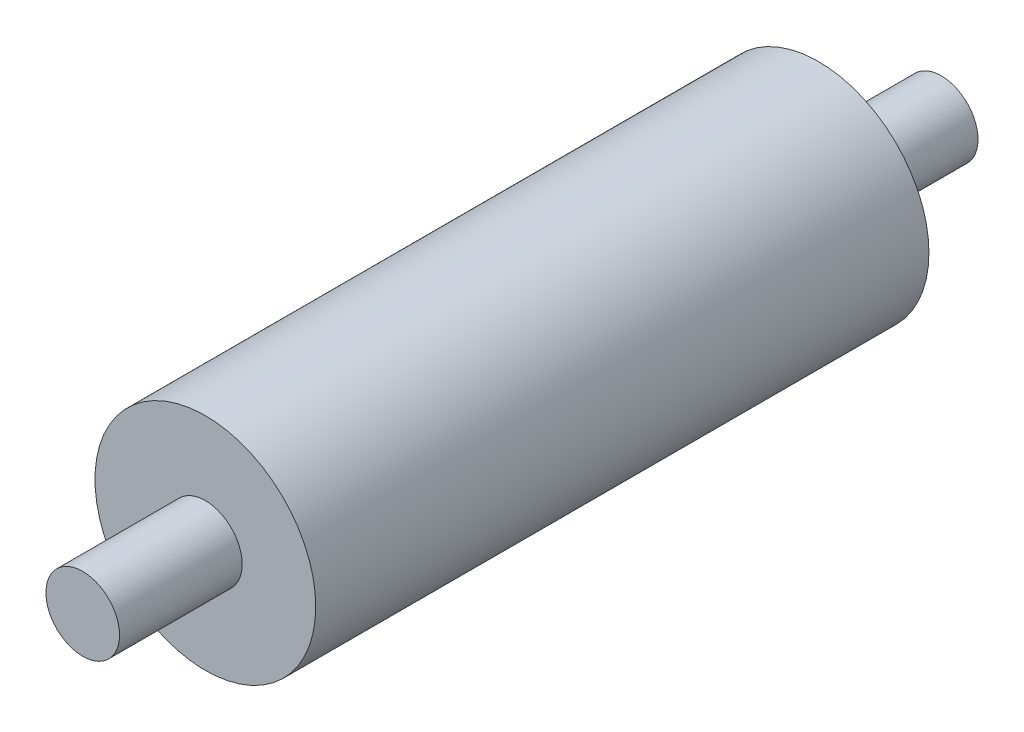
SolidWorks part; units mm, degrees
ref_plane "Front Plane" through (0, 0, 0) normal (0, 0, 1) x (1, 0, 0)
ref_plane "Top Plane" through (0, 0, 0) normal (0, 1, 0) x (1, 0, 0)
ref_plane "Right Plane" through (0, 0, 0) normal (1, 0, 0) x (0, 0, -1)
sketch "Sketch1" plane through (0, 0, 0) normal (0, 0, 1) x (1, 0, 0)
  circle A0 centre (0, 0) radius 9
  dimension "D1" = 18
extrude "Boss-Extrude1" add sketch "Sketch1" along normal blind 25 and the other way blind 25
sketch "Sketch2" plane through (0, 0, 25) normal (0, 0, 1) x (1, 0, 0)
  circle A0 centre (0, 0) radius 3
  dimension "D1" = 6
extrude "Boss-Extrude2" add sketch "Sketch2" along normal blind 10
mirror "Mirror1" about plane through (0, 0, 0) normal (0, 0, 1) of "Boss-Extrude2"
